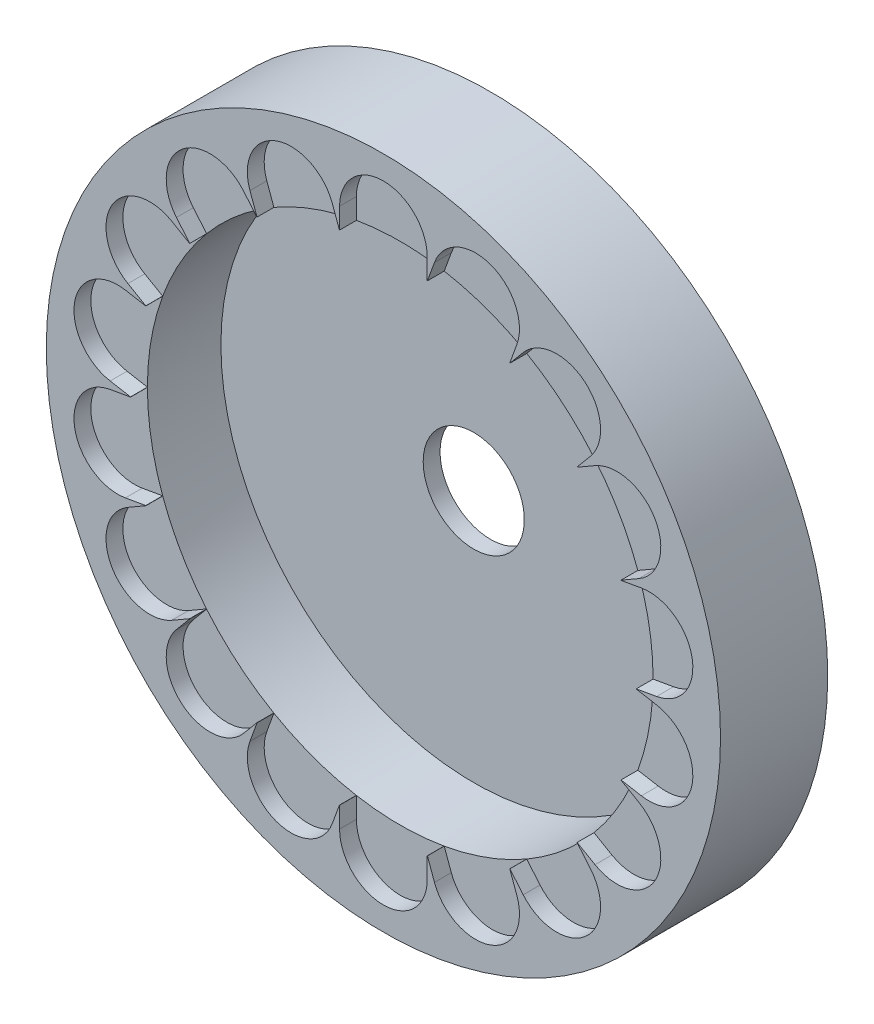
SolidWorks part; units mm, degrees
ref_plane "Front Plane" through (0, 0, 0) normal (0, 0, 1) x (1, 0, 0)
ref_plane "Top Plane" through (0, 0, 0) normal (0, 1, 0) x (1, 0, 0)
ref_plane "Right Plane" through (0, 0, 0) normal (1, 0, 0) x (0, 0, -1)
sketch "Sketch1" plane through (0, 0, 0) normal (0, 0, 1) x (1, 0, 0)
  circle A0 centre (0, 0) radius 63.5
  circle A1 centre (0, 0) radius 47.625
  dimension "D1" = 95.25
  dimension "D2" = 127
extrude "Boss-Extrude1" add sketch "Sketch1" along normal blind 17.018
sketch "Sketch2" plane through (0, 0, 17.018) normal (0, 0, 1) x (1, 0, 0)
  line L0 (0, 50.8) -> (0, -50.8) construction
  line L1 (8.255, 50.8) -> (8.255, -50.8)
  line L2 (-8.255, 50.8) -> (-8.255, -50.8)
  arc A0 (8.255, 50.8) -> (-8.255, 50.8) centre (0, 50.8) ccw
  arc A1 (-8.255, -50.8) -> (8.255, -50.8) centre (0, -50.8) ccw
  point P2 (0, 0)
  dimension "D2" = 8.255
  dimension "D1" = 101.6
extrude "Cut-Extrude1" cut sketch "Sketch2" against normal blind 3.175
pattern_circular "CirPattern1" count 10 every 20 about axis through (0, 0, 17.018) along (0, 0, -1) of "Cut-Extrude1" reverse direction yes
sketch "Sketch3" plane through (0, 0, 0) normal (0, 0, -1) x (-1, 0, 0)
  circle A0 centre (0, 0) radius 63.5
  circle A1 centre (0, 0) radius 9.525
  circle A2 centre (0, 0) radius 63.5 construction
  dimension "D1" = 19.05
extrude "Boss-Extrude2" add sketch "Sketch3" along normal blind 3.175
